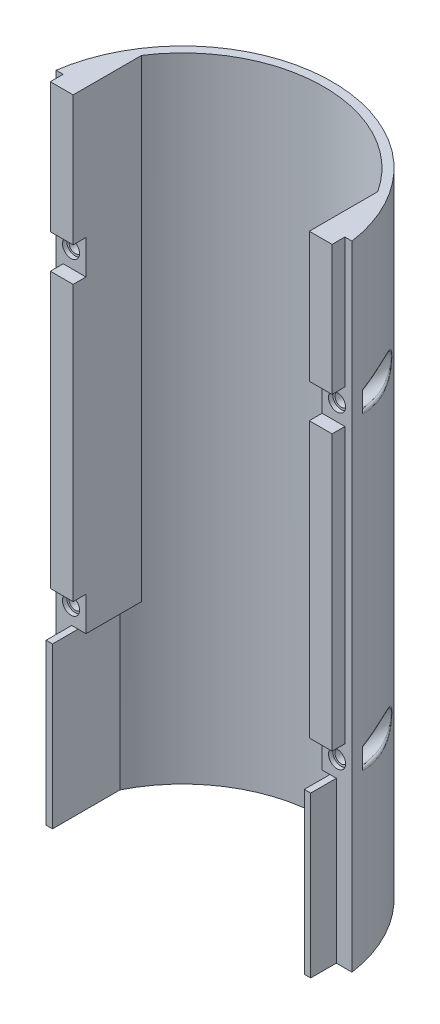
SolidWorks part; units mm, degrees
ref_plane "Front Plane" through (0, 0, 0) normal (0, 0, 1) x (1, 0, 0)
ref_plane "Top Plane" through (0, 0, 0) normal (0, 1, 0) x (1, 0, 0)
ref_plane "Right Plane" through (0, 0, 0) normal (1, 0, 0) x (0, 0, -1)
sketch "Sketch1" plane through (0, 0, 0) normal (0, 1, 0) x (1, 0, 0)
  line L0 (32.9848, -1) -> (34.9857, -1) construction
  line L1 (-32.9848, -1) -> (-34.9857, -1) construction
  line L2 (-34.641, 5) -> (-30.981, 5)
  line L3 (-30.981, 5) -> (-30.981, -1)
  line L4 (-30.981, -1) -> (-29.481, -1)
  line L5 (-29.481, -1) -> (-29.481, 14.828)
  line L6 (0, 0) -> (0, 33) construction
  line L7 (30.981, 5) -> (30.981, -1)
  line L8 (34.641, 5) -> (30.981, 5)
  line L9 (29.481, -1) -> (29.481, 14.828)
  line L10 (30.981, -1) -> (29.481, -1)
  arc A0 (32.9848, -1) -> (32.619, 5) centre (0, 0) ccw construction
  arc A1 (34.641, 5) -> (-34.641, 5) centre (0, 0) ccw
  arc A2 (-34.641, 5) -> (-34.9857, -1) centre (0, 0) ccw construction
  arc A3 (-32.619, 5) -> (-32.9848, -1) centre (0, 0) ccw construction
  arc A4 (-29.481, 14.828) -> (-32.619, 5) centre (0, 0) ccw construction
  arc A5 (-32.9848, -1) -> (32.9848, -1) centre (0, 0) ccw construction
  arc A6 (-34.9857, -1) -> (34.9857, -1) centre (0, 0) ccw construction
  arc A7 (32.619, 5) -> (29.481, 14.828) centre (0, 0) ccw construction
  arc A8 (29.481, 14.828) -> (-29.481, 14.828) centre (0, 0) ccw
  arc A9 (34.9857, -1) -> (34.641, 5) centre (0, 0) ccw construction
  dimension "D1" = 70
  dimension "D2" = 2
  dimension "D3" = 1
  dimension "D4" = 1.5
  dimension "D5" = 3.66
  dimension "D6" = 6
extrude "Boss-Extrude1" add sketch "Sketch1" along normal blind 37.5
sketch "Sketch2" plane through (0, 37.5, 0) normal (0, 1, 0) x (1, 0, 0)
  line L0 (-34.641, 5) -> (-27.641, 5)
  line L2 (-27.641, 5) -> (-27.641, 18.027)
  line L3 (34.641, 5) -> (27.641, 5)
  line L4 (27.641, 5) -> (27.641, 18.027)
  arc A0 (34.641, 5) -> (-34.641, 5) centre (0, 0) ccw construction
  arc A1 (34.641, 5) -> (-34.641, 5) centre (0, 0) ccw
  arc A2 (29.481, 14.828) -> (-29.481, 14.828) centre (0, 0) ccw construction
  arc A3 (27.641, 18.027) -> (-27.641, 18.027) centre (0, 0) ccw
  arc A4 (29.481, 14.828) -> (27.641, 18.027) centre (0, 0) ccw construction
  arc A5 (-27.641, 18.027) -> (-29.481, 14.828) centre (0, 0) ccw construction
  dimension "D1" = 7
extrude "Boss-Extrude2" add sketch "Sketch2" along normal blind 8
sketch "Sketch4" plane through (0, 45.5, 0) normal (0, 1, 0) x (1, 0, 0)
  line L0 (-32.981, 5) -> (-32.981, 2)
  line L1 (-32.981, 2) -> (-27.641, 2)
  line L2 (-27.641, 2) -> (-27.641, 5)
  line L3 (27.641, 5) -> (27.641, 2)
  line L4 (-34.641, 5) -> (-27.641, 5)
  line L5 (-27.641, 5) -> (-27.641, 18.027)
  line L6 (27.641, 18.027) -> (27.641, 5)
  line L7 (27.641, 5) -> (34.641, 5)
  line L8 (-34.641, 5) -> (-32.981, 5)
  line L9 (-27.641, 5) -> (-27.641, 18.027)
  line L10 (27.641, 18.027) -> (27.641, 5)
  line L11 (32.981, 5) -> (34.641, 5)
  line L12 (27.641, 2) -> (32.981, 2)
  line L13 (32.981, 2) -> (32.981, 5)
  line L14 (-32.981, 5) -> (-27.641, 5) construction
  line L15 (27.641, 5) -> (32.981, 5) construction
  arc A2 (34.641, 5) -> (-34.641, 5) centre (0, 0) ccw
  arc A3 (27.641, 18.027) -> (-27.641, 18.027) centre (0, 0) ccw
  arc A4 (34.641, 5) -> (-34.641, 5) centre (0, 0) ccw
  arc A5 (27.641, 18.027) -> (-27.641, 18.027) centre (0, 0) ccw
  point P9 (0, 0)
  dimension "D2" = 1.66
  dimension "D3" = 3
  dimension "D1" = 0
extrude "Boss-Extrude3" add sketch "Sketch4" along normal blind 64.33
sketch "Sketch5" plane through (0, 109.83, 0) normal (0, 1, 0) x (1, 0, 0)
  line L0 (-32.981, 5) -> (-27.641, 5)
  line L1 (-27.641, 2) -> (-27.641, 5) construction
  line L2 (-27.641, 5) -> (27.641, 5) construction
  line L3 (27.641, 5) -> (32.981, 5)
  line L4 (27.641, 5) -> (27.641, 2) construction
  line L8 (-34.641, 5) -> (-32.981, 5)
  line L9 (-32.981, 5) -> (-32.981, 2)
  line L10 (-32.981, 2) -> (-27.641, 2)
  line L11 (-27.641, 2) -> (-27.641, 18.027)
  line L12 (27.641, 18.027) -> (27.641, 2)
  line L13 (27.641, 2) -> (32.981, 2)
  line L14 (32.981, 2) -> (32.981, 5)
  line L15 (32.981, 5) -> (34.641, 5)
  line L16 (-34.641, 5) -> (-32.981, 5)
  line L17 (-32.981, 5) -> (-32.981, 2) construction
  line L18 (-32.981, 2) -> (-27.641, 2) construction
  line L19 (-27.641, 5) -> (-27.641, 18.027)
  line L20 (27.641, 18.027) -> (27.641, 5)
  line L21 (27.641, 2) -> (32.981, 2) construction
  line L22 (32.981, 2) -> (32.981, 5) construction
  line L23 (32.981, 5) -> (34.641, 5)
  arc A2 (27.641, 18.027) -> (-27.641, 18.027) centre (0, 0) ccw
  arc A3 (34.641, 5) -> (-34.641, 5) centre (0, 0) ccw
  arc A4 (27.641, 18.027) -> (-27.641, 18.027) centre (0, 0) ccw
  arc A5 (34.641, 5) -> (-34.641, 5) centre (0, 0) ccw
  dimension "D1" = 0
extrude "Boss-Extrude4" add sketch "Sketch5" along normal blind 8
sketch "Sketch6" plane through (0, 117.83, 0) normal (0, 1, 0) x (1, 0, 0)
  line L0 (27.641, 5) -> (34.641, 5) construction
  line L1 (32.981, 2) -> (32.981, 5) construction
  line L2 (27.641, 2) -> (32.981, 2) construction
  line L3 (27.641, 5) -> (27.641, 2) construction
  line L4 (27.641, 18.027) -> (27.641, 5) construction
  line L5 (-32.981, 2) -> (-27.641, 2) construction
  line L6 (-27.641, 2) -> (-27.641, 5) construction
  line L7 (-27.641, 5) -> (-27.641, 18.027) construction
  line L8 (-34.641, 5) -> (-27.641, 5) construction
  line L9 (-32.981, 5) -> (-32.981, 2) construction
  line L10 (32.981, 5) -> (34.641, 5)
  line L11 (32.981, 2) -> (32.981, 5)
  line L12 (27.641, 2) -> (32.981, 2)
  line L13 (27.641, 5) -> (27.641, 2)
  line L14 (27.641, 18.027) -> (27.641, 5)
  line L15 (-32.981, 2) -> (-27.641, 2)
  line L16 (-27.641, 2) -> (-27.641, 5)
  line L17 (-27.641, 5) -> (-27.641, 18.027)
  line L18 (-34.641, 5) -> (-32.981, 5)
  line L19 (-32.981, 5) -> (-32.981, 2)
  line L20 (-32.981, 5) -> (-27.641, 5) construction
  line L21 (27.641, 5) -> (32.981, 5) construction
  arc A0 (27.641, 18.027) -> (-27.641, 18.027) centre (0, 0) ccw construction
  arc A1 (34.641, 5) -> (-34.641, 5) centre (0, 0) ccw construction
  arc A2 (27.641, 18.027) -> (-27.641, 18.027) centre (0, 0) ccw
  arc A3 (34.641, 5) -> (-34.641, 5) centre (0, 0) ccw
extrude "Boss-Extrude5" add sketch "Sketch6" along normal offset from surface (30.42 mm away) 148.25 up to face at (0, 0, -9.3828)
sketch "Sketch7" plane through (0, 0, -5) normal (0, 0, 1) x (1, 0, 0)
  line L0 (27.641, 109.83) -> (34.641, 109.83) construction
  line L1 (34.641, 148.25) -> (34.641, 0) construction
  line L2 (-27.641, 109.83) -> (-34.641, 109.83) construction
  line L3 (-34.641, 148.25) -> (-34.641, 0) construction
  line L4 (27.641, 117.83) -> (27.641, 109.83) construction
  line L5 (-27.641, 45.5) -> (-27.641, 37.5) construction
  circle A0 centre (31.141, 113.83) radius 1.5
  circle A1 centre (-31.141, 113.83) radius 1.5
  circle A2 centre (31.141, 41.5) radius 1.5
  circle A3 centre (-31.141, 41.5) radius 1.5
  point P13 (31.141, 109.83)
  point P19 (-31.141, 109.83)
  point P20 (0, 0)
  point P23 (27.641, 113.83)
  point P26 (-27.641, 41.5)
  dimension "D1" = 3
extrude "Cut-Extrude1" cut sketch "Sketch7" against normal through all
sketch "Sketch8" plane through (0, 0, -5) normal (0, 0, 1) x (1, 0, 0)
  circle A11 centre (-31.141, 113.83) radius 3
  circle A12 centre (-31.141, 113.83) radius 3
  circle A14 centre (31.141, 113.83) radius 3
  circle A15 centre (31.141, 113.83) radius 3
  circle A17 centre (-31.141, 41.5) radius 3
  circle A18 centre (-31.141, 41.5) radius 3
  circle A20 centre (31.141, 41.5) radius 3
  circle A21 centre (31.141, 41.5) radius 3
  dimension "D1" = 1.5
  dimension "D2" = 1.5
  dimension "D3" = 1.5
  dimension "D4" = 1.5
extrude "Cut-Extrude2" cut sketch "Sketch8" against normal through all from offset 3 offset against normal yes
fillet "Fillet2" radius 0.5 4 edges at (-28.152, 113.5738, -20.7958) (28.152, 41.7562, -20.7958) (28.152, 114.0862, -20.7958) (-28.152, 41.2438, -20.7958)
sketch "Sketch9" plane through (0, 0, -5) normal (0, 0, 1) x (1, 0, 0)
  circle A2 centre (-31.141, 113.83) radius 2
  circle A3 centre (-31.141, 113.83) radius 2
  circle A5 centre (31.141, 113.83) radius 2
  circle A6 centre (31.141, 113.83) radius 2
  circle A8 centre (-31.141, 41.5) radius 2
  circle A9 centre (-31.141, 41.5) radius 2
  circle A11 centre (31.141, 41.5) radius 2
  circle A12 centre (31.141, 41.5) radius 2
  dimension "D1" = 0.5
  dimension "D2" = 0.5
  dimension "D3" = 0.5
  dimension "D4" = 0.5
extrude "Cut-Extrude3" cut sketch "Sketch9" against normal blind 1
